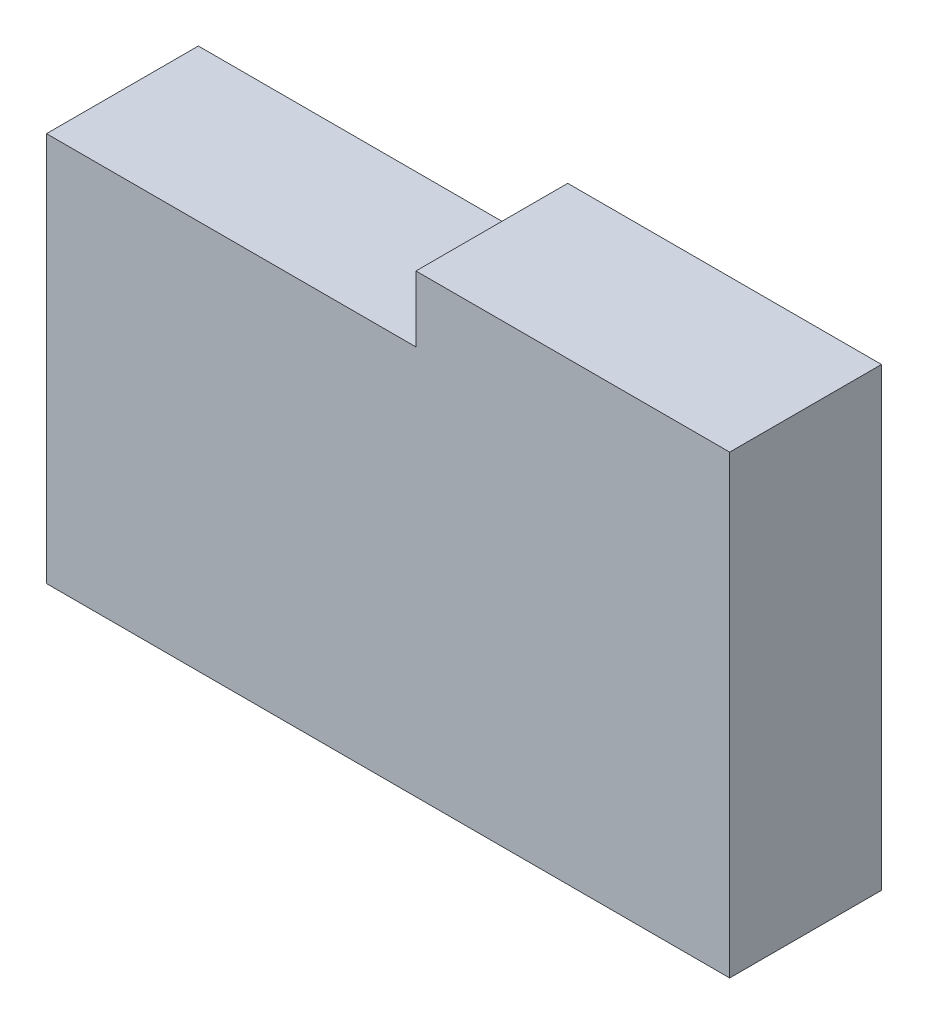
SolidWorks part; units mm, degrees
ref_plane "Plan de face" through (0, 0, 0) normal (0, 0, 1) x (1, 0, 0)
ref_plane "Plan de dessus" through (0, 0, 0) normal (0, 1, 0) x (1, 0, 0)
ref_plane "Plan de droite" through (0, 0, 0) normal (1, 0, 0) x (0, 0, -1)
sketch "Esquisse1" plane through (0, 0, 0) normal (0, 0, 1) x (1, 0, 0)
  line L0 (0, 0) -> (135, 0)
  line L1 (135, 0) -> (135, 90)
  line L2 (135, 90) -> (73, 90)
  line L3 (73, 90) -> (73, 77)
  line L4 (73, 77) -> (0, 77)
  line L5 (0, 77) -> (0, 0)
  dimension "D1" = 135
  dimension "D2" = 90
  dimension "D3" = 13
  dimension "D4" = 73
extrude "Boss.-Extru.1" add sketch "Esquisse1" against normal blind 30
sketch "Esquisse2" plane through (0, 0, 0) normal (0, 0, 1) x (1, 0, 0)
  text T0 "<b>Raspberry Pi 4</b>"
  text T1 "<b>DE0 Nano</b>\r\n\r\n"
  point P2 (0, 0)
